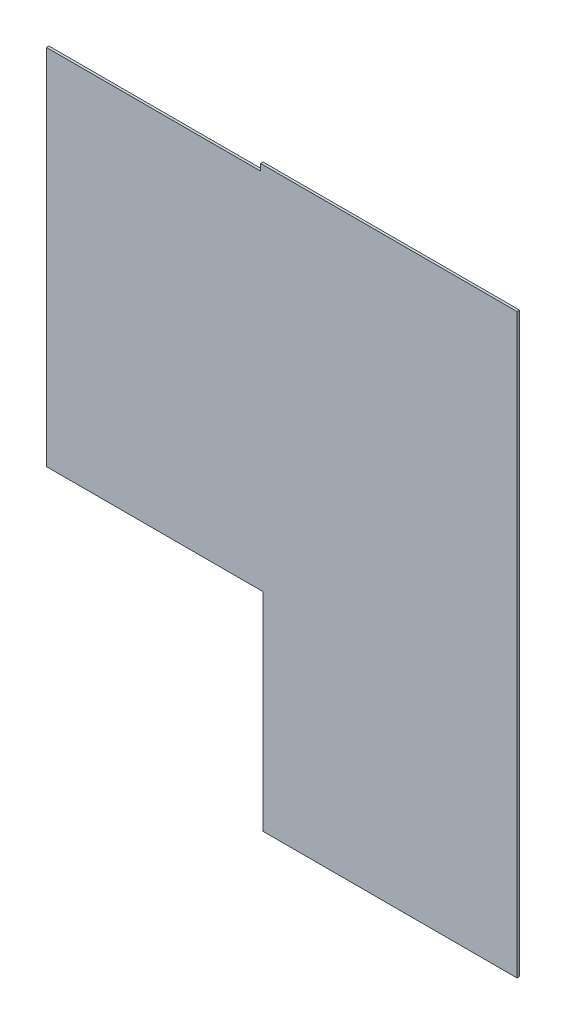
SolidWorks part; units mm, degrees
ref_plane "Спереди" through (0, 0, 0) normal (0, 0, 1) x (1, 0, 0)
ref_plane "Сверху" through (0, 0, 0) normal (0, 1, 0) x (1, 0, 0)
ref_plane "Справа" through (0, 0, 0) normal (1, 0, 0) x (0, 0, -1)
sketch "Эскиз2" plane through (0, 0, 0) normal (0, 0, 1) x (1, 0, 0)
  line L1 (1138.3, -949) -> (524, -949)
  line L2 (0, -447) -> (0, 431)
  line L3 (0, 431) -> (518, 431)
  line L4 (518, 431) -> (518, 447)
  line L5 (518, 447) -> (1138.3, 447)
  line L6 (1138.3, 447) -> (1138.3, -949)
  line L7 (0, -447) -> (524, -447)
  line L8 (524, -447) -> (524, -949)
extrude "Бобышка-Вытянуть1" add sketch "Эскиз2" against normal blind 6
equation "\"Ширина груза\"= 420"
equation "\"Глубина груза\"= 490"
equation "\"Высота груза\"= 297"
equation "\"Ширина ячейки\"= \"Ширина груза\" + 10"
equation "\"Глубина ячейки\"= \"Глубина груза\" + 10"
equation "\"Высота ячейки\"= \"Высота груза\" + 10 + 13"
equation "\"Колво ячеек ширина\"= 2"
equation "\"Колво ячеек высота\"= 2"
equation "\"Толщина стенки\" = 6"
equation "\"Крепление дверцы\"= 5"
equation "\"Ширина рейки\"= \"Толщина шестерни\""
equation "\"Высота рейки\"= 20"
equation "\"Высота пола\"= 20"
equation "\"Колво полозьев\"= 5"
equation "\"Отступ рейки\"= 20"
equation "\"Глубина каретки\"= \"Глубина ячейки\" + 30 + \"Мотор Y высота корпуса\" + 20"
equation "\"Длинна рейки\"= ( \"Ширина ячейки\" + \"Толщина стенки\" + \"Крепление дверцы\" ) * \"Колво ячеек ширина\" + \"Ширина ячейки выгрузки\" * \"Колво выгрузки\" + \"Толщина стенки\""
equation "\"Отступ шпильки\"= 26"
equation "\"Диаметр шпильки\"= 5"
equation "\"Длинна шпильки\"= ( \"Высота ячейки\" + \"Толщина стенки\" + \"Высота пола\" ) * \"Колво ячеек высота\" + ( \"Толщина стенки\" + \"Отступ рейки\" ) * 2 "
equation "\"Ширина пластины\"= 50  "
equation "\"Высота зона выгрузки\"= \"Высота ячейки\" * 2 + \"Толщина стенки\" * 2"
equation "\"Колво выгрузки\"= 1"
equation "\"Ширина ячейки выгрузки\"= \"Ширина ячейки\" + \"Толщина стенки\" + \"Отступ крепления мотора фиксации\"*2"
equation "\"Отступ крепления мотора фиксации\" = 30"
equation "\"Мотор X ширина корпуса\"= 42.3"
equation "\"Мотор X высота корпуса\"= 42.3"
equation "\"Мотор X длина корпуса\"= 40"
equation "\"Мотор X вылет вала\"= 19.8"
equation "\"Мотор Y ширина корпуса\"= 42.3"
equation "\"Мотор Y высота корпуса\"= 42.3"
equation "\"Мотор Y длина корпуса\"= 48"
equation "\"Мотор Y вылет вала\"= 30"
equation "\"Мотор Z ширина корпуса\"= 42"
equation "\"Мотор Z высота корпуса\"= 42"
equation "\"Мотор Z длина корпуса\"= 40"
equation "\"Мотор Z вылет вала\"= 23"
equation "\"Мотор диаметр вала ПРЕДВ\"= 5"
equation "\"Мотор шаг крепления ПРЕДВ\"= 31"
equation "\"Мотор диаметр отверстий ПРЕДВ\"= 3"
equation "\"Мотор глубина отверстий ПРЕДВ\"= 4.5"
equation "\"Мотор диаметр буртика ПРЕДВ\"= 22"
equation "\"Мотор высота буртика ПРЕДВ\"= 2"
equation "\"Мотор диаметр шкива ПРЕДВ\"= 16"
equation "\"Мотор длина шкива ПРЕДВ\"= 12"
equation "\"Мотор отступ шкива ПРЕДВ\"= 5"
equation "\"Мотор X шаг градусов\"= 1.8"
equation "\"Мотор Y шаг градусов\"= 1.8"
equation "\"Мотор Z шаг градусов\"= 1.8"
equation "\"Мотор Y диаметр ротора\"= 25.78"
equation "\"Толщина шестерни\"= 10"
equation "\"D1@Бобышка-Вытянуть1\"=\"Толщина стенки\""
